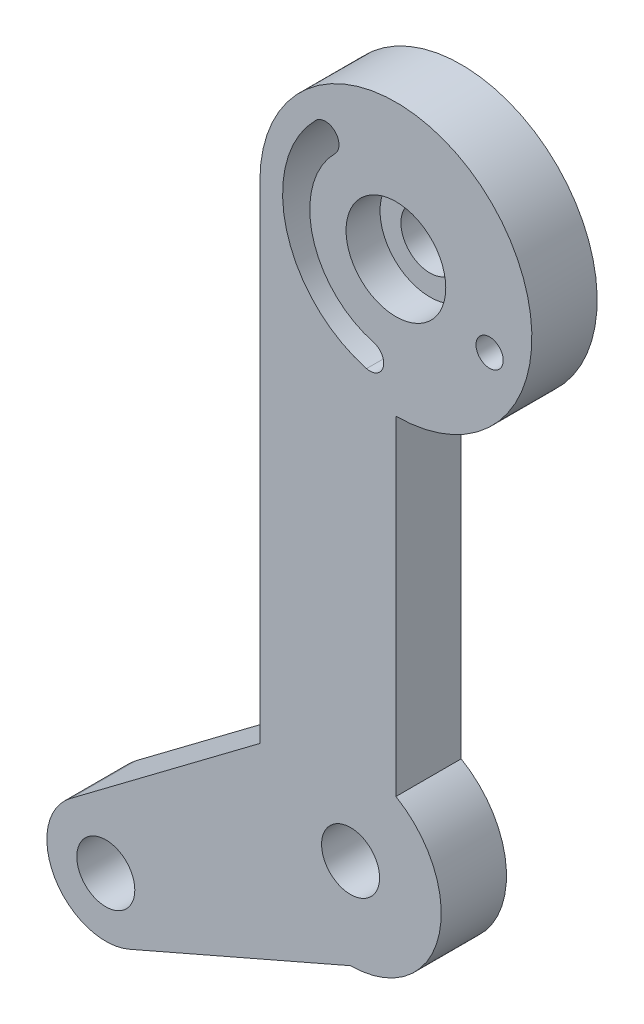
SolidWorks part; units mm, degrees
ref_plane "Front Plane" through (0, 0, 0) normal (0, 0, 1) x (1, 0, 0)
ref_plane "Top Plane" through (0, 0, 0) normal (0, 1, 0) x (1, 0, 0)
ref_plane "Right Plane" through (0, 0, 0) normal (1, 0, 0) x (0, 0, -1)
sketch "Sketch1" plane through (0, 0, 0) normal (0, 0, 1) x (1, 0, 0)
  line L0 (-5, 30) -> (-5, 3.1174)
  line L1 (2.5, 22.5) -> (2.5, 4.3301)
  line L2 (-12.2021, -10.3152) -> (0, -5)
  line L3 (-15.4525, -4.7374) -> (-5, 3.1174)
  circle A0 centre (0, 0) radius 1.6
  arc A1 (0, -5) -> (2.5, 4.3301) centre (0, 0) ccw
  circle A2 centre (-13.5, -7.3356) radius 1.6
  arc A3 (-15.4525, -4.7374) -> (-12.2021, -10.3152) centre (-13.5, -7.3356) ccw
  circle A4 centre (2.5, 30) radius 1.6
  arc A5 (2.5, 22.5) -> (-5, 30) centre (2.5, 30) ccw
  dimension "D1" = 3.2
  dimension "D4" = 5
  dimension "D5" = 3.25
  dimension "D6" = 7.5
  dimension "D7" = 12.2021
  dimension "D8" = 13.5
  dimension "D9" = 15.4525
  dimension "D10" = 22.5
extrude "Boss-Extrude1" add sketch "Sketch1" along normal blind 3.6
sketch "Sketch2" plane through (0, 0, 3.6) normal (0, 0, 1) x (1, 0, 0)
  line L0 (-5, 30) -> (-5, 3.1174) construction
  line L1 (2.5, 30) -> (-1.3891, 33.8891) construction
  line L2 (2.5, 30) -> (1.0765, 24.6874) construction
  line L3 (2.5, 30) -> (8, 30) construction
  line L4 (2.5, 30) -> (7.6683, 28.1189) construction
  circle A0 centre (7.6683, 28.1189) radius 0.75
  arc A1 (-0.8588, 33.3588) -> (-1.9194, 34.4194) centre (-1.3891, 33.8891) ccw
  arc A6 (0.8824, 23.963) -> (1.2706, 25.4119) centre (1.0765, 24.6874) ccw
  arc A7 (-1.9194, 34.4194) -> (0.8824, 23.963) centre (2.5, 30) ccw
  arc A8 (-0.8588, 33.3588) -> (1.2706, 25.4119) centre (2.5, 30) ccw
  dimension "D3" = 1.5
  dimension "D4" = 3.0806
  dimension "D2" = 120
  dimension "D1" = 6.25
  dimension "D5" = 20
extrude "Cut-Extrude1" cut sketch "Sketch2" against normal through all
sketch "Sketch3" plane through (0, 0, 0) normal (0, 0, -1) x (-1, 0, 0)
  circle A0 centre (-2.5, 30) radius 2.75
  dimension "D1" = 5.5
extrude "Cut-Extrude2" [suppressed] cut sketch "Sketch3" against normal blind 1.875
sketch "Sketch4" plane through (0, 0, 3.6) normal (0, 0, 1) x (1, 0, 0)
  circle A0 centre (2.5, 30) radius 2.75
  dimension "D1" = 5.5
extrude "Cut-Extrude3" cut sketch "Sketch4" against normal blind 1.875
sketch "Sketch5" [suppressed] plane through (0, 0, 3.6) normal (0, 0, 1) x (1, 0, 0)
  line L0 (0, 0) -> (-13.5, -7.3356) construction
sketch "Sketch6" plane through (0, 0, 3.6) normal (0, 0, 1) x (1, 0, 0)
  line L0 (0, 0) -> (-13.5, -7.3356) construction
